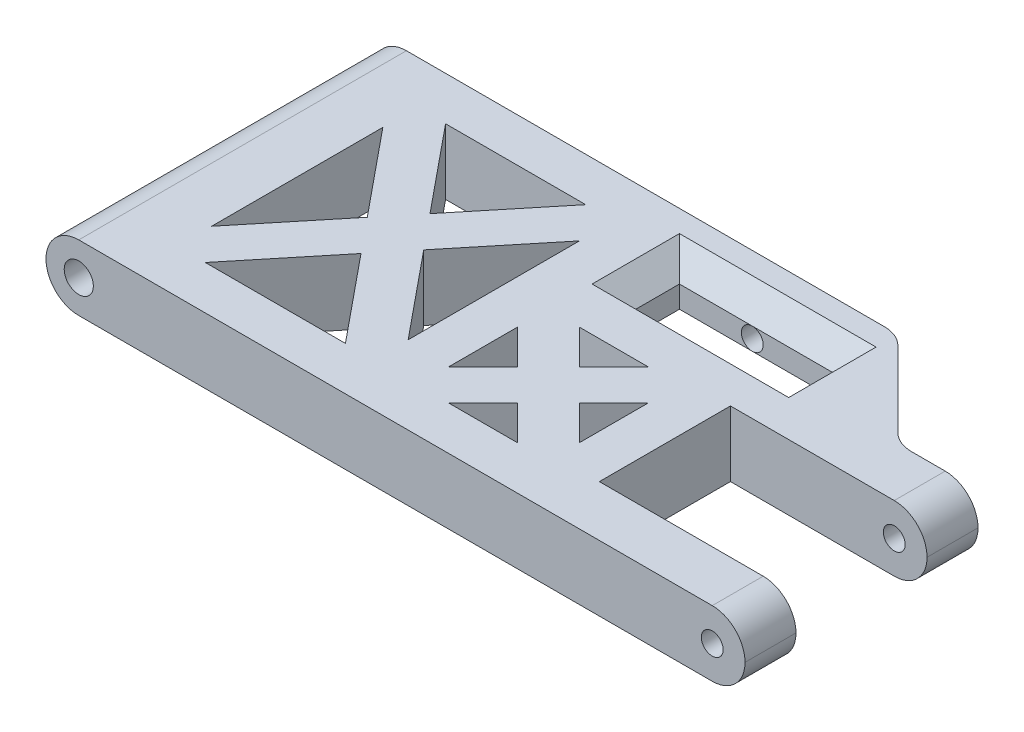
SolidWorks part; units mm, degrees
ref_plane "Front Plane" through (0, 0, 0) normal (0, 0, 1) x (1, 0, 0)
ref_plane "Top Plane" through (0, 0, 0) normal (0, 1, 0) x (1, 0, 0)
ref_plane "Right Plane" through (0, 0, 0) normal (1, 0, 0) x (0, 0, -1)
sketch "Sketch1" plane through (0, 0, 0) normal (0, 1, 0) x (1, 0, 0)
  line L1 (0, 0) -> (72, 0)
  line L2 (0, 0) -> (0, 45)
  line L3 (0, 45) -> (72, 45)
  line L4 (72, 0) -> (72, 45)
extrude "Boss-Extrude1" add sketch "Sketch1" along normal blind 9
sketch "Sketch3" plane through (0, 0, 0) normal (0, 1, 0) x (1, 0, 0)
  line L1 (69, 32) -> (96, 32)
  line L2 (69, 32) -> (69, 25)
  line L3 (69, 25) -> (96, 25)
  line L4 (96, 32) -> (96, 25)
extrude "Boss-Extrude3" add sketch "Sketch3" along normal blind 9
sketch "Sketch4" plane through (0, 0, 0) normal (0, 1, 0) x (1, 0, 0)
  line L2 (69, 0) -> (96, 0)
  line L3 (69, 0) -> (69, 7)
  line L4 (69, 7) -> (96, 7)
  line L5 (96, 0) -> (96, 7)
  point P0 (48.3281, 13.8634)
extrude "Boss-Extrude4" add sketch "Sketch4" along normal blind 9
sketch "Sketch5" plane through (0, 9, 0) normal (0, 1, 0) x (1, 0, 0)
  line L1 (72, 25) -> (69, 25)
  line L2 (72, 25) -> (72, 7)
  line L3 (72, 7) -> (69, 7)
  line L4 (69, 25) -> (69, 7)
extrude "Cut-Extrude1" cut sketch "Sketch5" against normal blind 9
sketch "Sketch6" plane through (0, 9, 0) normal (0, 1, 0) x (1, 0, 0)
  line L0 (72, 45) -> (72, 32)
  line L1 (72, 32) -> (85, 32)
  line L2 (96, 32) -> (72, 32) construction
  line L3 (85, 32) -> (72, 45)
extrude "Boss-Extrude5" add sketch "Sketch6" against normal blind 9
fillet "Fillet1" radius 4.5 8 edges at (0, 0, -22.5) (0, 9, -22.5) (72, 4.5, -45) (85, 4.5, -32) (96, 0, -3.5) (96, 9, -3.5) (96, 0, -28.5) (96, 9, -28.5)
hole_wizard "Ø4.0mm Dowel Hole1" positions "Sketch7" profile "Sketch8" hole size "Ø4.0" standard "ANSI Metric" end condition through all
sketch "Sketch7" plane through (0, 0, -45) normal (0, 0, -1) x (-1, 0, 0)
  point P0 (-4.5, 4.5)
  point P3 (0, 0)
sketch "Sketch8" plane through (4.5, 4.5, -45) normal (1, 0, 0) x (0, 1, 0)
  line L0 (0, 0) -> (0, 45)
  line L1 (0, 45) -> (2, 45)
  line L2 (2, 45) -> (2, 0)
  line L5 (2, 0) -> (0, 0)
  line L11 (0, -6.35) -> (0, 107.95) construction
  dimension "Thru Hole Dia." = 4
  dimension "Thru Hole Depth" = 45
hole_wizard "Ø3.0mm Dowel Hole1" positions "Sketch9" profile "Sketch10" hole size "Ø3.0" standard "ANSI Metric" end condition through all
sketch "Sketch9" plane through (0, 0, 0) normal (0, 0, 1) x (1, 0, 0)
  point P0 (91.5, 4.5)
  point P4 (0, 0)
sketch "Sketch10" plane through (91.5, 4.5, 0) normal (1, 0, 0) x (0, -1, 0)
  line L0 (0, 0) -> (0, 45)
  line L1 (0, 45) -> (1.5, 45)
  line L2 (1.5, 45) -> (1.5, 0)
  line L5 (1.5, 0) -> (0, 0)
  line L11 (0, -6.35) -> (0, 107.95) construction
  dimension "Thru Hole Dia." = 3
  dimension "Thru Hole Depth" = 45
sketch "Sketch12" plane through (0, 9, 0) normal (0, 1, 0) x (1, 0, 0)
  line L9 (48, 39) -> (69, 39)
  line L10 (48, 39) -> (48, 33)
  line L11 (48, 33) -> (69, 33)
  line L12 (69, 39) -> (69, 33)
  point P2 (0, 0)
  point P5 (0, 0)
  point P6 (0, 0)
extrude "Cut-Extrude3" cut sketch "Sketch12" against normal blind 9
chamfer "Chamfer1" distance 3 angle 45 8 edges at (58.5, 0, -33) (48, 0, -36) (58.5, 0, -39) (69, 0, -36) (69, 9, -36) (58.5, 9, -33) (48, 9, -36) (58.5, 9, -39)
hole_wizard "Ø3.0mm Dowel Hole2" positions "Sketch13" profile "Sketch15" hole size "Ø3.0" standard "ANSI Metric"
sketch "Sketch13" plane through (0, 0, -45) normal (0, 0, -1) x (-1, 0, 0)
  point P0 (-58, 4.5)
sketch "Sketch15" plane through (58, 4.5, -45) normal (1, 0, 0) x (0, 1, 0)
  line L0 (0, 0) -> (0, 18.9013)
  line L1 (0, 18.9013) -> (1.5, 18)
  line L2 (1.5, 18) -> (1.5, 0)
  line L5 (1.5, 0) -> (0, 0)
  line L10 (0, 18.9013) -> (-1.5, 18) construction
  line L11 (0, -6.35) -> (0, 107.95) construction
  dimension "Hole Dia." = 3
  dimension "Hole Depth" = 18
  dimension "Drill Angle" = 118
sketch "Sketch16" plane through (0, 9, 0) normal (0, 1, 0) x (1, 0, 0)
  line L0 (45, 30) -> (45, 42) construction
  line L1 (12, 39) -> (39, 39)
  line L2 (12, 39) -> (12, 6)
  line L3 (12, 6) -> (39, 6)
  line L4 (39, 39) -> (39, 6)
  line L5 (70.136, 45) -> (4.5, 45) construction
  line L6 (4.5, 0) -> (91.5, 0) construction
  line L7 (0, 0) -> (0, 45) construction
  line L8 (69, 25) -> (69, 7) construction
  line L9 (45, 24) -> (63, 24)
  line L10 (45, 24) -> (45, 6)
  line L11 (45, 6) -> (63, 6)
  line L12 (63, 24) -> (63, 6)
  line L13 (72, 30) -> (45, 30) construction
  dimension "D1" = 6
  dimension "D2" = 6
  dimension "D3" = 6
  dimension "D4" = 12
  dimension "D5" = 6
  dimension "D6" = 6
  dimension "D7" = 6
extrude "Cut-Extrude4" cut sketch "Sketch16" against normal blind 9
sketch "Sketch17" plane through (0, 9, 0) normal (0, 1, 0) x (1, 0, 0)
  line L1 (39, 6) -> (41.3219, 7.8997)
  line L2 (41.3219, 7.8997) -> (14.3219, 40.8997)
  line L3 (14.3219, 40.8997) -> (12, 39)
  line L4 (12, 39) -> (9.6781, 37.1003)
  line L5 (9.6781, 37.1003) -> (36.6781, 4.1003)
  line L6 (36.6781, 4.1003) -> (39, 6)
  point P8 (36.7812, 3.9809)
  dimension "D1" = 3
  dimension "D2" = 3
extrude "Boss-Extrude7" add sketch "Sketch17" against normal blind 9
sketch "Sketch18" plane through (0, 9, 0) normal (0, 1, 0) x (1, 0, 0)
  line L0 (12, 6) -> (14.3219, 4.1003)
  line L1 (14.3219, 4.1003) -> (41.3219, 37.1003)
  line L3 (39, 39) -> (41.3219, 37.1003)
  line L4 (39, 39) -> (36.6781, 40.8997)
  line L5 (36.6781, 40.8997) -> (9.6781, 7.8997)
  line L6 (9.6781, 7.8997) -> (12, 6)
  point P4 (0, 0)
extrude "Boss-Extrude8" add sketch "Sketch18" against normal blind 9
sketch "Sketch19" plane through (0, 9, 0) normal (0, 1, 0) x (1, 0, 0)
  line L1 (45, 6) -> (42.8787, 8.1213)
  line L2 (42.8787, 8.1213) -> (60.8787, 26.1213)
  line L3 (60.8787, 26.1213) -> (63, 24)
  line L4 (65.1213, 21.8787) -> (47.1213, 3.8787)
  line L5 (47.1213, 3.8787) -> (45, 6)
  line L6 (63, 24) -> (65.1213, 21.8787)
  line L8 (63, 6) -> (65.1213, 8.1213)
  line L9 (65.1213, 8.1213) -> (47.1213, 26.1213)
  line L10 (47.1213, 26.1213) -> (45, 24)
  line L11 (42.8787, 21.8787) -> (60.8787, 3.8787)
  line L12 (60.8787, 3.8787) -> (63, 6)
  line L13 (45, 24) -> (42.8787, 21.8787)
  line M27 (63, 6) -> (45, 6)
  line M28 (45, 6) -> (45, 24)
  line M29 (45, 24) -> (63, 24)
  line M30 (63, 24) -> (63, 6)
extrude "Boss-Extrude10" add sketch "Sketch19" against normal blind 9 contours L4 L11 L9 M27 M30 | L11 L2 L9 M28 M29 | L9 L4 L2 M30 M29 | L11 L2 L4 M28 M27 | L2 L11 L4 L9 region at (48.9374, 9, -9.9374) region at (54, 9, -15) region at (59.0626, 9, -9.9374) region at (48.9374, 9, -20.0626) region at (59.0626, 9, -20.0626)
